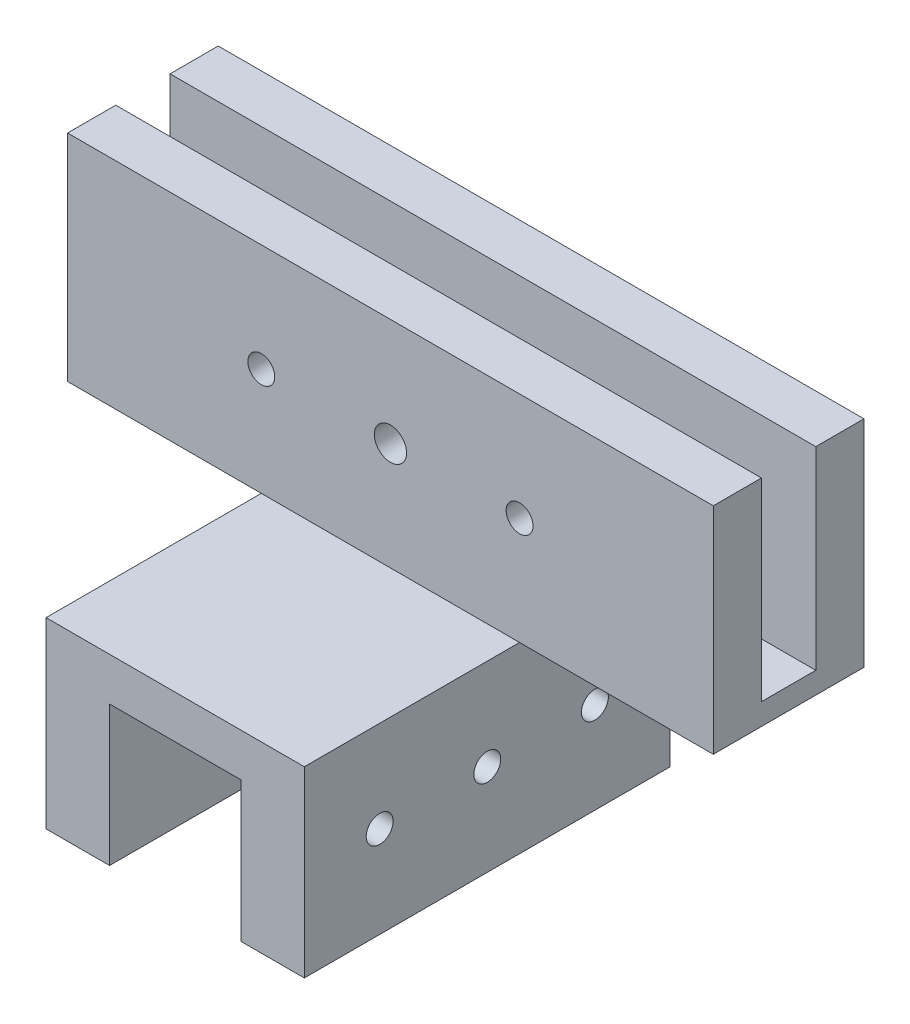
SolidWorks part; units mm, degrees
ref_plane "Ebene vorne" through (0, 0, 0) normal (0, 0, 1) x (1, 0, 0)
ref_plane "Ebene oben" through (0, 0, 0) normal (0, 1, 0) x (1, 0, 0)
ref_plane "Ebene rechts" through (0, 0, 0) normal (1, 0, 0) x (0, 0, -1)
sketch "Sketch1" plane through (0, 0, 0) normal (0, 0, 1) x (1, 0, 0)
  line L1 (-6, 0) -> (6, 0)
  line L2 (-6, 0) -> (-6, -6.5)
  line L3 (-6, -6.5) -> (6, -6.5)
  line L4 (6, 0) -> (6, -6.5)
  line L5 (-6, 0) -> (6, -6.5) construction
  line L6 (-6, -6.5) -> (6, 0) construction
  line L7 (16.5, 0) -> (-16.5, 0) construction
  line L8 (0, -9.075) -> (0, 9.075) construction
  line L9 (-6, 0) -> (6, 0)
  line L10 (-3.05, -6.5) -> (3.05, -6.5)
  line L11 (-3.05, -6.5) -> (-3.05, 0)
  line L12 (-3.05, 0) -> (3.05, 0)
  line L13 (3.05, -6.5) -> (3.05, 0)
  line L14 (-3.05, -6.5) -> (3.05, 0) construction
  line L15 (-3.05, 0) -> (3.05, -6.5) construction
  line L16 (-6, 0) -> (-6, 2)
  line L17 (6, 0) -> (6, 2)
  line L18 (-6, 2) -> (6, 2)
  line L20 (-15, 12) -> (15, 12)
  line L21 (-15, 12) -> (-15, 2)
  line L22 (-15, 2) -> (15, 2)
  line L23 (15, 12) -> (15, 2)
  line L24 (-15, 12) -> (15, 2) construction
  line L25 (-15, 2) -> (15, 12) construction
  point P0 (0, -3.25)
  point P9 (0, 7)
  point P10 (0, -3.25)
  point P21 (0, 0)
  dimension "D1" = 12
  dimension "D2" = 0
  dimension "D3" = 6.5
  dimension "D4" = 0
  dimension "D5" = 6.1
  dimension "D6" = 2
  dimension "D7" = 30
  dimension "D8" = 10
  dimension "D9" = 0
extrude "Boss-Extrude1" add sketch "Sketch1" along normal blind 10 and the other way blind 7 contours L18 L16 L1 L9 L17 | L13 L3 L4 L1 | L3 L11 L1 L2 region at (0, 1, 0) region at (-4.525, -3.25, 0) region at (4.525, -3.25, 0)
extrude "Boss-Extrude2" add sketch "Sketch1<3>" against normal blind 7 contours L21 L22 L23 L20
sketch "Sketch1<3>" plane through (0, 0, 0) normal (0, 0, 1) x (1, 0, 0) same geometry as "Sketch1"
sketch "Sketch3" plane through (-15, 0, 0) normal (-1, 0, 0) x (0, 0, 1)
  line L0 (-7, 12) -> (0, 12) construction
  line L1 (-2.2385, 12) -> (-4.7615, 12)
  line L2 (-2.2385, 12) -> (-2.2385, 3)
  line L3 (-2.2385, 3) -> (-4.7615, 3)
  line L4 (-4.7615, 12) -> (-4.7615, 3)
  line L5 (-2.2385, 12) -> (-4.7615, 3) construction
  line L6 (-2.2385, 3) -> (-4.7615, 12) construction
  line L7 (-7, 2) -> (0, 2) construction
  point P0 (-3.5, 7.5)
  dimension "D1" = 1
extrude "Cut-Extrude1" cut sketch "Sketch3" against normal through all
hole_wizard "M1.6x0.35 Tapped Hole1" positions "Sketch7" profile "Sketch5" tap size "M1.6x0.35" standard "ANSI Metric" end condition up to next
sketch "Sketch7" plane through (0, 0, 0) normal (0, 0, 1) x (1, 0, 0)
  point P2 (6, 7)
  point P4 (-6, 7)
sketch "Sketch5" plane through (6, 7, 0) normal (1, 0, 0) x (0, -1, 0)
  line L0 (0, 0) -> (0, 2.2385)
  line L1 (0, 2.2385) -> (0.625, 2.2385)
  line L2 (0.625, 2.2385) -> (0.625, 0)
  line L5 (0.625, 0) -> (0, 0)
  line L11 (0, -6.35) -> (0, 107.95) construction
  dimension "Thru Tap Drill Dia." = 1.25
  dimension "Thru Tap Drill Depth" = 2.2385
cosmetic thread "Hole Thread1" parameters "D2"=1.6
cosmetic thread "Hole Thread2" parameters "D2"=1.6
hole_wizard "M1.6x0.35 Tapped Hole2" positions "Sketch8" profile "Sketch9" tap size "M1.6x0.35" standard "ANSI Metric" end condition up to next
sketch "Sketch8" plane through (6, 0, 0) normal (1, 0, 0) x (0, 0, -1)
  line L0 (-10, -2.25) -> (7, -2.25) construction
  line L2 (7, -6.5) -> (7, 2) construction
  line L4 (-10, -6.5) -> (-10, 2) construction
  line L6 (-6.5, -0.1885) -> (3.5, -0.1885)
  line L7 (-6.5, -0.1885) -> (-6.5, -4.3115)
  line L8 (-6.5, -4.3115) -> (3.5, -4.3115)
  line L9 (3.5, -0.1885) -> (3.5, -4.3115)
  line L10 (-6.5, -0.1885) -> (3.5, -4.3115) construction
  line L11 (-6.5, -4.3115) -> (3.5, -0.1885) construction
  point P0 (3.5, -2.25)
  point P2 (-6.5, -2.25)
  point P160 (-1.5, -2.25)
  point P474 (-6.5, -2.25)
  point P475 (3.5, -2.25)
  dimension "D1" = 3.5
sketch "Sketch9" plane through (6, -2.25, -3.5) normal (0, 1, 0) x (0, 0, -1)
  line L0 (0, 0) -> (0, 2.95)
  line L1 (0, 2.95) -> (0.625, 2.95)
  line L2 (0.625, 2.95) -> (0.625, 0)
  line L5 (0.625, 0) -> (0, 0)
  line L11 (0, -6.35) -> (0, 107.95) construction
  dimension "Thru Tap Drill Dia." = 1.25
  dimension "Thru Tap Drill Depth" = 2.95
cosmetic thread "Hole Thread3" parameters "D2"=1.6
cosmetic thread "Hole Thread4" parameters "D2"=1.6
cosmetic thread "Hole Thread5" parameters "D2"=1.6
hole_wizard "Ø1.5mm Dowel Hole1" positions "Sketch10" profile "Sketch11" hole size "Ø1.5" standard "ANSI Metric" end condition through all
sketch "Sketch10" plane through (0, 0, 0) normal (0, 0, 1) x (1, 0, 0)
  line L0 (-6, 7) -> (6, 7) construction
  point P0 (0, 7)
  point P14 (0, 0)
  point P15 (0, 7)
sketch "Sketch11" plane through (0, 7, 0) normal (1, 0, 0) x (0, -1, 0)
  line L0 (0, 0) -> (0, 7)
  line L1 (0, 7) -> (0.75, 7)
  line L2 (0.75, 7) -> (0.75, 0)
  line L5 (0.75, 0) -> (0, 0)
  line L11 (0, -6.35) -> (0, 107.95) construction
  dimension "Thru Hole Dia." = 1.5
  dimension "Thru Hole Depth" = 7
